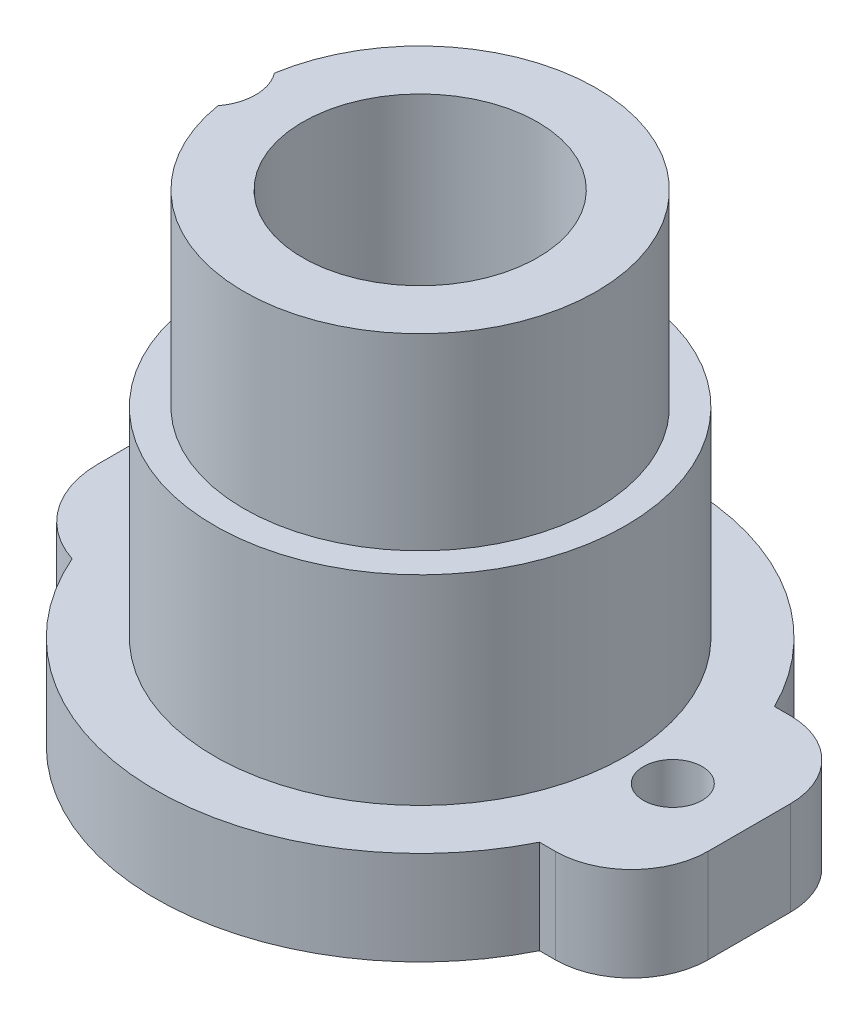
SolidWorks part; units mm, degrees
material "PET"
ref_plane "前视基准面" through (0, 0, 0) normal (0, 0, 1) x (1, 0, 0)
ref_plane "上视基准面" through (0, 0, 0) normal (0, 1, 0) x (1, 0, 0)
ref_plane "右视基准面" through (0, 0, 0) normal (1, 0, 0) x (0, 0, -1)
other "Configuration Table"
sketch "草图8" plane through (0, 0, 0) normal (0, 0, 1) x (1, 0, 0)
  line L0 (20, 0) -> (45, 0)
  line L1 (45, 0) -> (45, 16)
  line L2 (45, 16) -> (35, 16)
  line L3 (35, 16) -> (35, 50)
  line L4 (35, 50) -> (30, 50)
  line L5 (30, 50) -> (30, 82)
  line L6 (30, 82) -> (20, 82)
  line L7 (20, 82) -> (20, 0)
  line L8 (0, -10) -> (0, 92) construction
revolve "旋转1" add sketch "草图8" angle 360 about L8
sketch "草图9" plane through (0, 0, 0) normal (0, 1, 0) x (1, 0, 0)
  line L1 (-53, 18) -> (0, 18)
  line L2 (-53, 18) -> (-53, -18)
  line L3 (-53, -18) -> (0, -18)
  line L4 (0, 18) -> (0, -18)
extrude "凸台-拉伸1" add sketch "草图9" along normal blind 16
sketch "草图10" plane through (0, 0, 0) normal (0, 1, 0) x (1, 0, 0)
  line L1 (0, 20) -> (56, 20)
  line L2 (0, 20) -> (0, -20)
  line L3 (0, -20) -> (56, -20)
  line L4 (56, 20) -> (56, -20)
extrude "凸台-拉伸2" add sketch "草图10" along normal blind 16
sketch "草图11" plane through (0, 0, 0) normal (0, 1, 0) x (1, 0, 0)
  circle A0 centre (-36, 0) radius 8
extrude "切除-拉伸3" cut sketch "草图11" along normal blind 82
sketch "草图12" plane through (0, 0, 0) normal (0, 1, 0) x (1, 0, 0)
  circle A0 centre (43, 0) radius 5
extrude "切除-拉伸6" cut sketch "草图12" along normal blind 82
fillet "圆角1" radius 17 1 edges at (-53, 8, 18) tangent propagation no
fillet "圆角2" radius 13 2 edges at (56, 8, -20) (56, 8, 20) tangent propagation no
